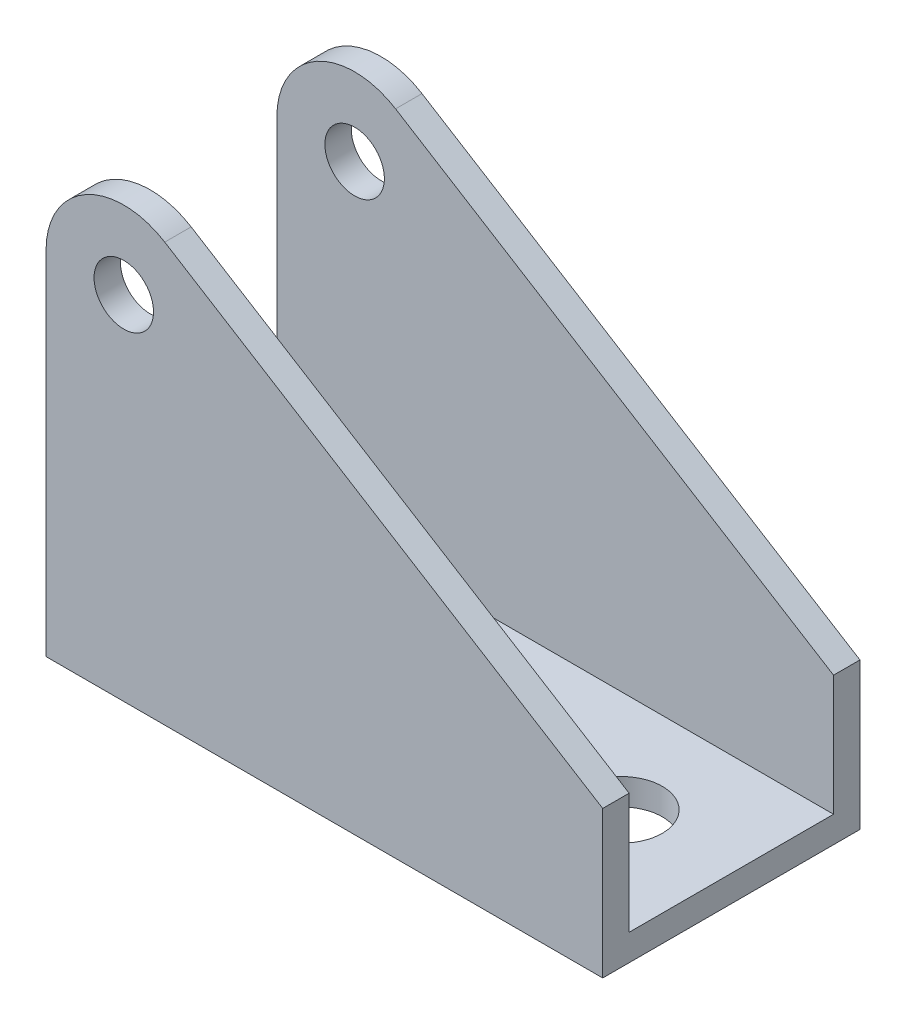
SolidWorks part; units mm, degrees
ref_plane "Front Plane" through (0, 0, 0) normal (0, 0, 1) x (1, 0, 0)
ref_plane "Top Plane" through (0, 0, 0) normal (0, 1, 0) x (1, 0, 0)
ref_plane "Right Plane" through (0, 0, 0) normal (1, 0, 0) x (0, 0, -1)
sketch "Sketch1" plane through (0, 0, 0) normal (0, 1, 0) x (1, 0, 0)
  line L0 (-36.5, 4.25) -> (-46.55, 4.25)
  line L1 (-46.55, -13.4) -> (11.45, -13.4)
  line L2 (-46.55, -13.4) -> (-46.55, 13.4)
  line L3 (-46.55, 13.4) -> (11.45, 13.4)
  line L4 (11.45, -13.4) -> (11.45, 13.4)
  line L5 (-36.5, -4.25) -> (-46.55, -4.25)
  circle A0 centre (0, 0) radius 4.25
  circle A1 centre (-36.5, 0) radius 4.25
  point P4 (11.45, 0)
  dimension "D1" = 8.5
  dimension "D4" = 7.2
  dimension "D5" = 28
  dimension "D2" = 26.8
  dimension "D3" = 58
extrude "Boss-Extrude1" add sketch "Sketch1" along normal blind 2.75 contours A1 L5 L2 L1 L4 L3 L0 A0 region at (-16.4381, 0, 0)
sketch "Sketch2" plane through (0, 0, 0) normal (0, 0, 1) x (1, 0, 0)
  line L0 (-46.55, 0) -> (-46.55, 36.7)
  line L1 (-34.1826, 43.5847) -> (11.45, 15.3)
  line L4 (11.45, 15.3) -> (11.45, 0)
  line L5 (11.45, 0) -> (-46.55, 0)
  arc A0 (-46.55, 36.7) -> (-34.1826, 43.5847) centre (-38.45, 36.7) cw
  circle A1 centre (-38.45, 36.7) radius 3.1
  point P5 (-35.8246, 42.862)
  dimension "D2" = 6.2
  dimension "D3" = 33.6
  dimension "D1" = 15.3
  dimension "D4" = 5
extrude "Boss-Extrude2" add sketch "Sketch2" against normal blind 2.75 from surface starting at face at (-17.55, 1.375, 13.4)
extrude "Boss-Extrude3" add sketch "Sketch2<2>" along normal blind 2.75 from surface starting at face at (-17.55, 1.375, -13.4)
sketch "Sketch2<2>" plane through (0, 0, 0) normal (0, 0, 1) x (1, 0, 0) same geometry as "Sketch2"
